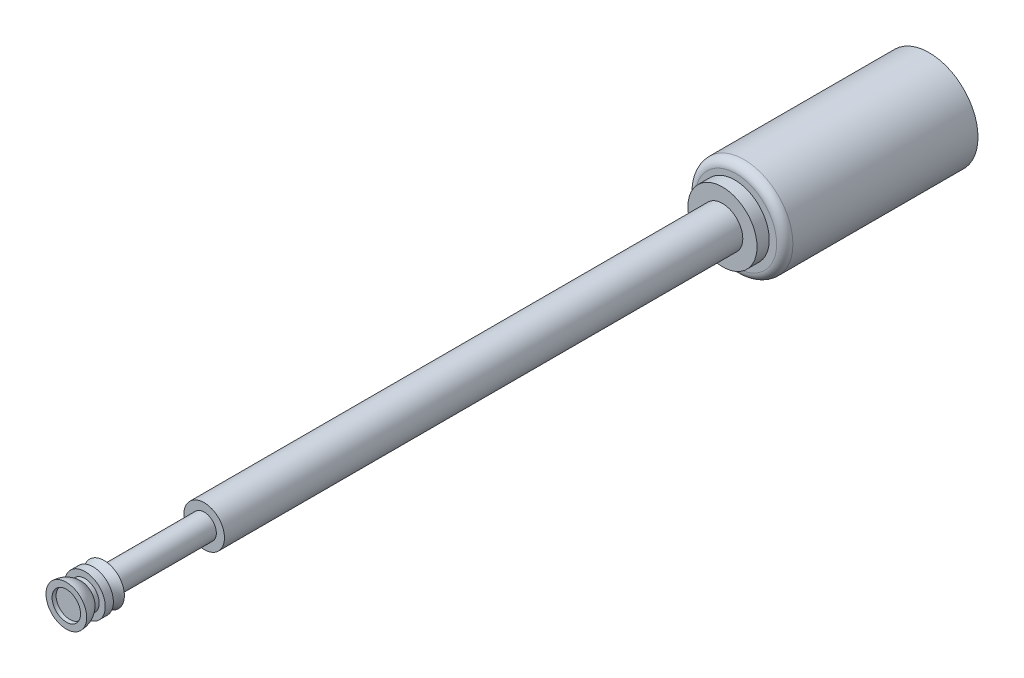
SolidWorks part; units mm, degrees
ref_plane "Front Plane" through (0, 0, 0) normal (0, 0, 1) x (1, 0, 0)
ref_plane "Top Plane" through (0, 0, 0) normal (0, 1, 0) x (1, 0, 0)
ref_plane "Right Plane" through (0, 0, 0) normal (1, 0, 0) x (0, 0, -1)
sketch "Sketch1" plane through (0, 0, 0) normal (0, 0, 1) x (1, 0, 0)
  circle A0 centre (0, 0) radius 0.5
  circle A1 centre (0.0316, 0) radius 1.2
  dimension "D1" = 1
  dimension "D2" = 2.4
extrude "Boss-Extrude1" add sketch "Sketch1" along normal blind 15.5 contours A0 region at (0, 0, 0)
extrude "Boss-Extrude2" add sketch "Sketch1<3>" against normal blind 4.75 contours A0 | A1 A0 region at (0, 0, 0) region at (-1.1345, 0, 0)
sketch "Sketch1<3>" plane through (0, 0, 0) normal (0, 0, 1) x (1, 0, 0) same geometry as "Sketch1"
fillet "Fillet1" radius 0.2 1 edges at (1.2316, 0, 0)
sketch "Sketch2" plane through (0, 0, 0) normal (0, 0, 1) x (1, 0, 0)
  circle A0 centre (0, 0) radius 0.85
  dimension "D1" = 1.7
extrude "Boss-Extrude3" add sketch "Sketch2" along normal blind 0.3
sketch "Sketch3" plane through (0, 0, 0) normal (0, 1, 0) x (1, 0, 0)
  line L0 (0, -15.5) -> (0, -16.0775)
  line L1 (-0.5, -15.5) -> (0.5, -15.5) construction
  line L2 (0.35, -16.4275) -> (0.5, -16.4275)
  line L3 (0.35, -16.0704) -> (0.35, -15.9704)
  line L4 (0.35, -15.9704) -> (0.5, -15.9704)
  line L5 (0.5, -15.9704) -> (0.5, -15.7704)
  line L6 (0.5, -15.7704) -> (0.4, -15.7704)
  line L7 (0, -15.5) -> (0.5, -15.5)
  arc A0 (0, -16.0775) -> (0.35, -16.4275) centre (0, -16.4275) cw
  arc A1 (0.5, -16.4275) -> (0.35, -16.0704) centre (0, -16.4275) ccw
  arc A2 (0.4, -15.7704) -> (0.5, -15.5) centre (0.899, -15.8013) cw
  dimension "D2" = 0.35
  dimension "D3" = 0.5
  dimension "D1" = 0.9275
  dimension "D4" = 0.1
  dimension "D5" = 0.2
  dimension "D6" = 0.15
  dimension "D7" = 0.1
revolve "Revolve2" add sketch "Sketch3" angle 360 about L0
sketch "Sketch4" plane through (0, 0, 0) normal (0, 1, 0) x (1, 0, 0)
  line L0 (0, -15.5) -> (0, -16.427) construction
  line L1 (0.5, -15.5) -> (-0.5, -15.5) construction
  line L3 (0.0005, -16.34) -> (-0.445, -16.34)
  line L4 (0.0005, -16.34) -> (0.0005, -16.24)
  line L5 (0.0005, -16.24) -> (-0.445, -16.24)
  line L6 (-0.445, -16.34) -> (-0.445, -16.24)
  line L7 (0.0005, -16.34) -> (-0.445, -16.24) construction
  line L8 (0.0005, -16.24) -> (-0.445, -16.34) construction
  point P5 (-0.2222, -16.29)
  point P10 (-0.2222, -16.24)
  dimension "D1" = 0.84
  dimension "D2" = 0.1
revolve "Revolve3" add sketch "Sketch4" angle 360 about L4
sketch "Sketch5" plane through (0, 0, 0) normal (0, 1, 0) x (1, 0, 0)
  line L0 (0.5, -15.5) -> (-0.5, -15.5) construction
  line L1 (-0.3, -15.5) -> (-1.0731, -15.5)
  line L2 (-0.3, -15.5) -> (-0.3, -13.04)
  line L3 (-0.3, -13.04) -> (-1.0731, -13.04)
  line L4 (-1.0731, -15.5) -> (-1.0731, -13.04)
  line L5 (0, -15.5) -> (0, -16.4275) construction
  line L6 (-0.5, -16.4275) -> (0.5, -16.4275) construction
  point P10 (-0.1485, -12.718)
  dimension "D1" = 2.46
  dimension "D2" = 0.6
revolve "Revolve4" add sketch "Sketch5" angle 360 about L5
sketch "Sketch7" plane through (0, 0, -4.75) normal (0, 0, -1) x (-1, 0, 0)
  point P0 (0, 0)
revolve "Cut-Revolve1" cut sketch "Sketch5<2>" angle 360 about L5
sketch "Sketch5<2>" plane through (0, 0, 0) normal (0, 1, 0) x (1, 0, 0) same geometry as "Sketch5"
